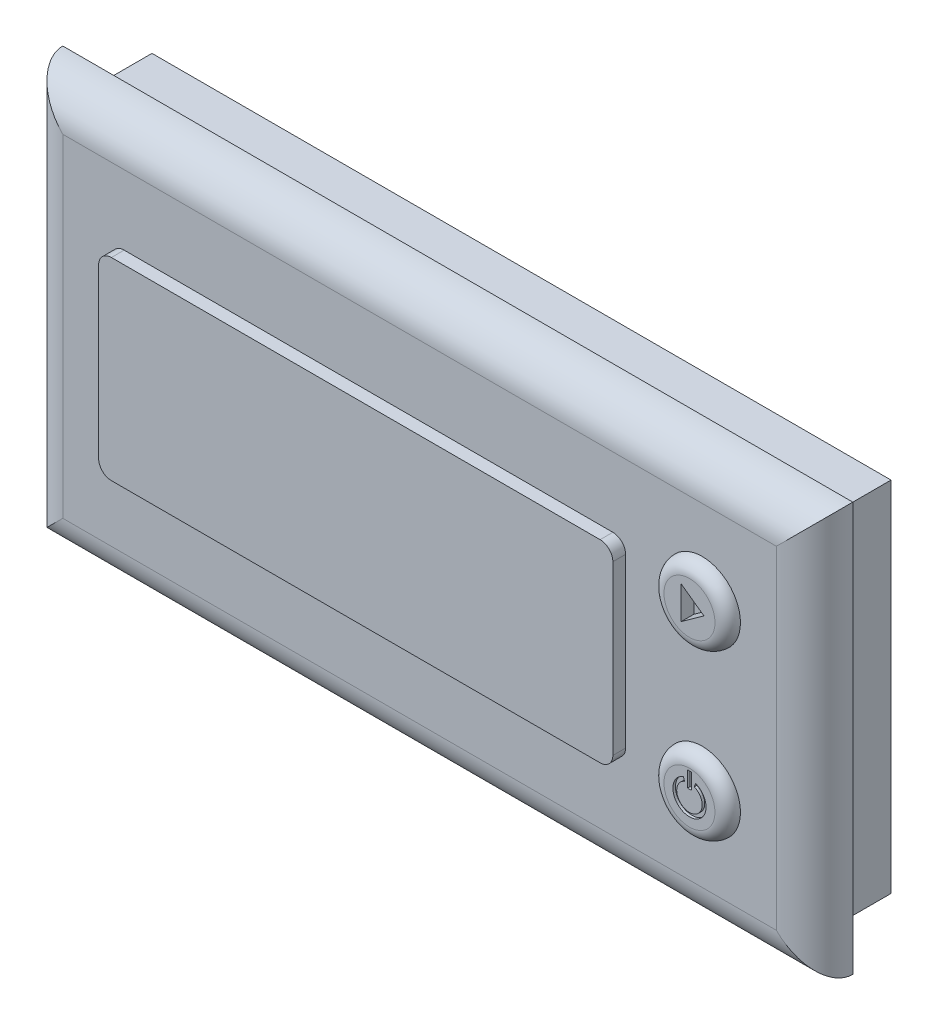
SolidWorks part; units mm, degrees
ref_plane "Front Plane" through (0, 0, 0) normal (0, 0, 1) x (1, 0, 0)
ref_plane "Top Plane" through (0, 0, 0) normal (0, 1, 0) x (1, 0, 0)
ref_plane "Right Plane" through (0, 0, 0) normal (1, 0, 0) x (0, 0, -1)
sketch "Sketch1" plane through (0, 0, 0) normal (0, 0, 1) x (1, 0, 0)
  line L1 (29, -14.05) -> (-29, -14.05)
  line L2 (29, -14.05) -> (29, 14.05)
  line L3 (29, 14.05) -> (-29, 14.05)
  line L4 (-29, -14.05) -> (-29, 14.05)
  line L5 (29, -14.05) -> (-29, 14.05) construction
  line L6 (29, 14.05) -> (-29, -14.05) construction
  point P0 (0, 0)
  dimension "D1" = 58
  dimension "D2" = 28.1
extrude "Boss-Extrude1" add sketch "Sketch1" along normal blind 5
sketch "Sketch2" plane through (0, 0, 5) normal (0, 0, 1) x (1, 0, 0)
  line L0 (31, 16.05) -> (-31, 16.05)
  line L1 (-31, 16.05) -> (-31, -16.05)
  line L2 (-31, -16.05) -> (31, -16.05)
  line L3 (31, -16.05) -> (31, 16.05)
  line L4 (-29, 14.05) -> (-29, -14.05)
  line L5 (-29, -14.05) -> (29, -14.05)
  line L6 (29, -14.05) -> (29, 14.05)
  line L7 (29, 14.05) -> (-29, 14.05)
  line L8 (-29, 14.05) -> (-29, -14.05) construction
  line L9 (-29, -14.05) -> (29, -14.05) construction
  line L10 (29, -14.05) -> (29, 14.05) construction
  line L11 (29, 14.05) -> (-29, 14.05) construction
  dimension "D1" = 0
  dimension "D2" = 2
extrude "Boss-Extrude2" add sketch "Sketch2" along normal blind 3
fillet "Fillet1" radius 3 4 edges at (0, -16.05, 8) (-31, 0, 8) (0, 16.05, 8) (31, 0, 8)
sketch "Sketch3" plane through (0, 0, 8) normal (0, 0, 1) x (1, 0, 0)
  line L4 (16.1686, 0) -> (31, 0) construction
  line L5 (-24.1861, 7.5832) -> (16.1686, 7.5832)
  line L6 (-24.1861, 7.5832) -> (-24.1861, -7.5832)
  line L7 (-24.1861, -7.5832) -> (16.1686, -7.5832)
  line L8 (16.1686, 7.5832) -> (16.1686, -7.5832)
  line L9 (-24.1861, 7.5832) -> (16.1686, -7.5832) construction
  line L10 (-24.1861, -7.5832) -> (16.1686, 7.5832) construction
  line L11 (31, -16.05) -> (31, 16.05) construction
  circle A0 centre (22.1817, 6.4474) radius 3.0006
  circle A1 centre (22.1817, -6.4474) radius 3.0006
  point P2 (-4.0087, 0)
  point P11 (0, 0)
  point P12 (22.1817, 6.4474)
extrude "Boss-Extrude3" add sketch "Sketch3" along normal blind 1 contours L5 L8 L7 L6
extrude "Boss-Extrude4" add sketch "Sketch3<6>" along normal blind 1 contours A0 | A1
sketch "Sketch3<6>" plane through (0, 0, 8) normal (0, 0, 1) x (1, 0, 0) same geometry as "Sketch3"
fillet "Fillet2" radius 1 2 edges at (19.1811, -6.4474, 9) (25.1824, 6.4474, 9)
sketch "Sketch4" plane through (0, 0, 9) normal (0, 0, 1) x (1, 0, 0)
  line L0 (21.5268, 7.7638) -> (21.5268, 5.1908)
  line L1 (21.5268, 5.1908) -> (23.3128, 6.4773)
  line L2 (23.3128, 6.4773) -> (21.5268, 7.7638)
extrude "Cut-Extrude2" cut sketch "Sketch4" against normal blind 1
sketch "Sketch5" plane through (0, 0, 9) normal (0, 0, 1) x (1, 0, 0)
  line L0 (22.1817, -6.4474) -> (22.1817, -4.4468) construction
  line L1 (22.3817, -6.4474) -> (22.3817, -4.4468) construction
  line L2 (21.9817, -6.4474) -> (21.9817, -4.4468) construction
  line L3 (21.9817, -4.4468) -> (22.3817, -4.4468) construction
  line L4 (21.9817, -6.4474) -> (22.3817, -6.4474) construction
  line L5 (22.6627, -5.239) -> (22.5597, -5.5209)
  line L6 (21.7008, -5.239) -> (21.8038, -5.5209)
  line L7 (22.3317, -5.8698) -> (22.3317, -4.6312)
  line L8 (22.0317, -5.8698) -> (22.0317, -4.6312)
  line L9 (22.0317, -5.8698) -> (22.3317, -5.8698)
  line L10 (22.3317, -6.4474) -> (22.3317, -4.4468) construction
  line L11 (22.0317, -6.4474) -> (22.0317, -4.4468) construction
  circle A4 centre (22.1817, -6.4474) radius 2.0006 construction
  arc A7 (21.7008, -5.239) -> (22.6627, -5.239) centre (22.1817, -6.4474) ccw
  arc A8 (21.8038, -5.5209) -> (22.5597, -5.5209) centre (22.1817, -6.4474) ccw
  arc A9 (22.3317, -4.6312) -> (22.0317, -4.6312) centre (22.1817, -6.4474) ccw
  dimension "D3" = 0.2
  dimension "D4" = 0.2
  dimension "D5" = 0.15
  dimension "D6" = 0.15
extrude "Cut-Extrude3" cut sketch "Sketch5" against normal blind 0.2
fillet "Fillet3" radius 1 4 edges at (-24.1861, 7.5832, 8.5) (-24.1861, -7.5832, 8.5) (16.1686, -7.5832, 8.5) (16.1686, 7.5832, 8.5)
